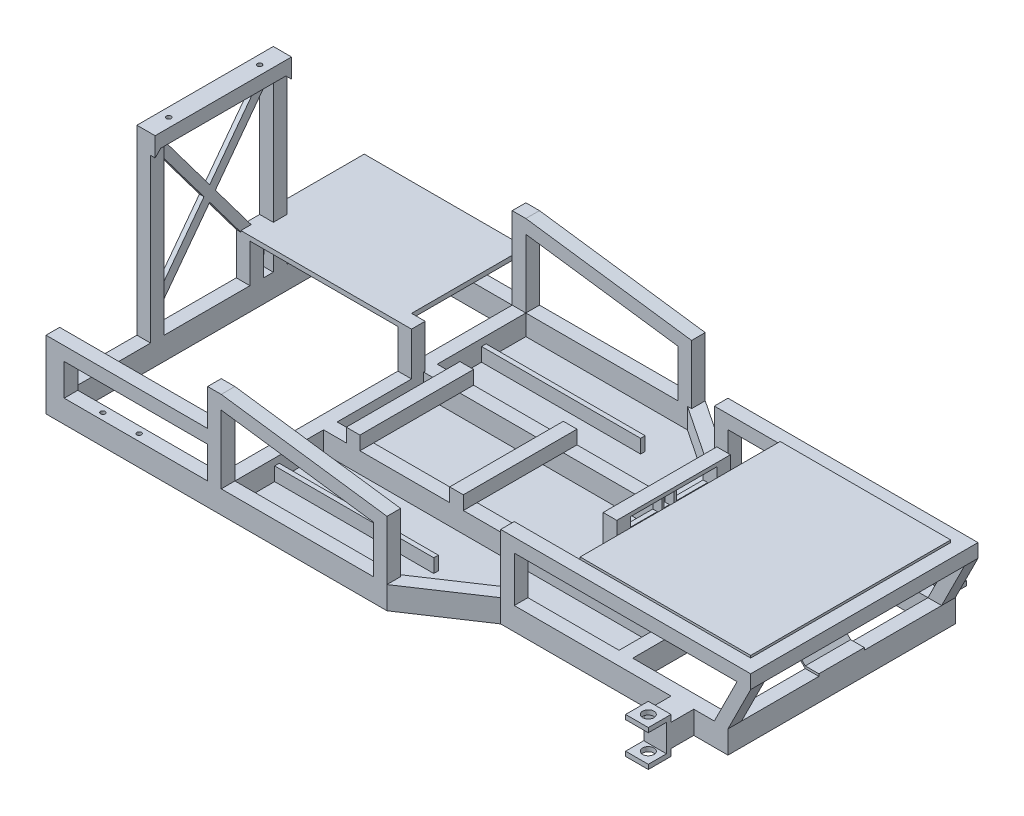
SolidWorks part; units mm, degrees
ref_plane "Front Plane" through (0, 0, 0) normal (0, 0, 1) x (1, 0, 0)
ref_plane "Top Plane" through (0, 0, 0) normal (0, 1, 0) x (1, 0, 0)
ref_plane "Right Plane" through (0, 0, 0) normal (1, 0, 0) x (0, 0, -1)
sketch "Sketch1" plane through (0, 0, 0) normal (0, 1, 0) x (1, 0, 0)
  line L1 (-65, 35) -> (10, 35)
  line L2 (-65, 35) -> (-65, -35)
  line L3 (-65, -35) -> (10, -35)
  line L4 (75, 25) -> (75, -25)
  line L6 (25, 25) -> (10, 35)
  line L9 (25, -25) -> (10, -35)
  line L10 (25, 25) -> (75, 25)
  line L11 (25, -25) -> (75, -25)
  line L12 (-62, 32) -> (-62, -32)
  line L13 (-62, -32) -> (-29.4542, -32)
  line L14 (24.0917, -22) -> (9.0917, -32)
  line L15 (24.0917, -22) -> (48.0458, -22)
  line L16 (72, 22) -> (72, -22)
  line L17 (24.0917, 22) -> (48.0458, 22)
  line L18 (24.0917, 22) -> (9.0917, 32)
  line L19 (-62, 32) -> (-29.4542, 32)
  line L20 (-26.4542, 32) -> (-26.4542, 12.5)
  line L21 (-29.4542, 32) -> (-29.4542, -32)
  line L22 (-26.4542, 32) -> (9.0917, 32)
  line L23 (-62, 32) -> (9.0917, 32) construction
  line L24 (-26.4542, -32) -> (9.0917, -32)
  line L25 (-62, -32) -> (9.0917, -32) construction
  line L27 (51.0458, 22) -> (51.0458, -22)
  line L28 (51.0458, 22) -> (72, 22)
  line L29 (24.0917, 22) -> (72, 22) construction
  line L30 (51.0458, -22) -> (72, -22)
  line L31 (24.0917, -22) -> (72, -22) construction
  line L32 (48.0458, 22) -> (48.0458, 12.5)
  line L33 (48.0458, 12.5) -> (-26.4542, 12.5)
  line L34 (-26.4542, -12.5) -> (-26.4542, -32)
  line L35 (-26.4542, 9.5) -> (48.0458, 9.5)
  line L36 (75, 0) -> (-65, 0) construction
  line L37 (48.0458, -12.5) -> (-26.4542, -12.5)
  line L38 (-26.4542, -9.5) -> (48.0458, -9.5)
  line L39 (48.0458, 9.5) -> (48.0458, -9.5)
  line L41 (48.0458, -12.5) -> (48.0458, -22)
  line L42 (-26.4542, 9.5) -> (-26.4542, -9.5)
  line L43 (-26.4542, 32) -> (-26.4542, -32) construction
  point P0 (0, 0)
  dimension "D1" = 70
  dimension "D2" = 75
  dimension "D3" = 75
  dimension "D4" = 50
  dimension "D6" = 3
  dimension "D7" = 15
  dimension "D5" = 3
extrude "Boss-Extrude1" add sketch "Sketch1" along normal mid plane 5
sketch "Sketch2" plane through (0, -2.5, 0) normal (0, -1, 0) x (1, 0, 0)
  line L0 (9.0917, 32) -> (24.0917, 22)
  line L1 (-26.4542, 32) -> (9.0917, 32)
  line L2 (-26.4542, 32) -> (-26.4542, -32)
  line L3 (-26.4542, -32) -> (9.0917, -32)
  line L5 (24.0917, 22) -> (48.0458, 22)
  line L6 (48.0458, 22) -> (48.0458, -22)
  line L7 (48.0458, -22) -> (24.0917, -22)
  line L8 (24.0917, -22) -> (9.0917, -32)
extrude "Boss-Extrude3" add sketch "Sketch2" against normal blind 0.5
sketch "Sketch3" plane through (0, 0, 25) normal (0, 0, 1) x (1, 0, 0)
  line L2 (25, -2.5) -> (75, -2.5) construction
  line L3 (62.4798, 2.5) -> (67.4798, 2.5)
  line L4 (62.4798, 2.5) -> (62.4798, -2.5)
  line L5 (62.4798, -2.5) -> (67.4798, -2.5)
  line L6 (67.4798, 2.5) -> (67.4798, -2.5)
  line L7 (62.4798, 2.5) -> (67.4798, -2.5) construction
  line L8 (62.4798, -2.5) -> (67.4798, 2.5) construction
  dimension "D1" = 5
  dimension "D2" = 5
extrude "Boss-Extrude4" add sketch "Sketch3" along normal blind 5
sketch "Sketch6" plane through (0, 0, 30) normal (0, 0, 1) x (1, 0, 0)
  line L0 (75, 2.5) -> (75, -2.5) construction
  line L1 (62.4798, 4) -> (67.4798, 4)
  line L2 (62.4798, 4) -> (62.4798, -4)
  line L3 (62.4798, -4) -> (67.4798, -4)
  line L4 (67.4798, 4) -> (67.4798, -4)
  point P0 (64.9798, 0)
  point P5 (64.9798, 4)
  point P9 (75, 0)
  dimension "D1" = 8
  dimension "D2" = 5
  dimension "D4" = 4
extrude "Boss-Extrude5" add sketch "Sketch6" along normal blind 1
sketch "Sketch7" plane through (0, 4, 0) normal (0, 1, 0) x (1, 0, 0)
  line L0 (62.4798, -30) -> (67.4798, -30)
  line L1 (67.4798, -30) -> (67.4798, -35)
  line L2 (67.4798, -35) -> (62.4798, -35)
  line L3 (62.4798, -35) -> (62.4798, -30)
extrude "Boss-Extrude7" add sketch "Sketch7" against normal blind 8
sketch "Sketch8" plane through (0, 0, 35) normal (0, 0, 1) x (1, 0, 0)
  line L9 (62.4798, -4) -> (62.4798, 4) construction
  line L10 (62.4798, 3) -> (67.4798, 3)
  line L11 (67.4798, -4) -> (67.4798, 4) construction
  line L12 (67.4798, 3) -> (67.4798, -3)
  line L13 (67.4798, -3) -> (62.4798, -3)
  line L14 (62.4798, -3) -> (62.4798, 3)
extrude "Cut-Extrude1" cut sketch "Sketch8" against normal blind 4
sketch "Sketch9" plane through (0, 4, 0) normal (0, 1, 0) x (1, 0, 0)
  circle A0 centre (64.9798, -32.5) radius 1.25
  dimension "D1" = 2.5
extrude "Cut-Extrude2" cut sketch "Sketch9" against normal through all
sketch "Sketch10" plane through (0, 0, -25) normal (0, 0, -1) x (-1, 0, 0)
  line L3 (-67.4798, 2.5) -> (-62.4798, 2.5)
  line L4 (-67.4798, 2.5) -> (-67.4798, -2.5)
  line L5 (-67.4798, -2.5) -> (-62.4798, -2.5)
  line L6 (-62.4798, 2.5) -> (-62.4798, -2.5)
  dimension "D1" = 5
  dimension "D2" = 5
extrude "Boss-Extrude10" add sketch "Sketch10" along normal blind 5
sketch "Sketch12" plane through (0, 0, -30) normal (0, 0, -1) x (-1, 0, 0)
  line L2 (-67.4798, 4) -> (-62.4798, 4)
  line L3 (-67.4798, 4) -> (-67.4798, -4)
  line L4 (-67.4798, -4) -> (-62.4798, -4)
  line L5 (-62.4798, 4) -> (-62.4798, -4)
extrude "Boss-Extrude11" add sketch "Sketch12" along normal blind 5
sketch "Sketch13" plane through (0, 0, -35) normal (0, 0, -1) x (-1, 0, 0)
  line L1 (-67.4798, 4) -> (-67.4798, -4) construction
  line L2 (-67.4798, 3) -> (-62.4798, 3)
  line L3 (-62.4798, -4) -> (-62.4798, 4) construction
  line L4 (-62.4798, 3) -> (-62.4798, -3)
  line L5 (-62.4798, -3) -> (-67.4798, -3)
  line L6 (-67.4798, -3) -> (-67.4798, 3)
extrude "Cut-Extrude3" cut sketch "Sketch13" against normal blind 4
sketch "Sketch14" plane through (0, 4, 0) normal (0, 1, 0) x (1, 0, 0)
  circle A0 centre (64.9798, 32.5) radius 1.25
extrude "Cut-Extrude4" cut sketch "Sketch14" against normal through all
sketch "Sketch16" plane through (-65, 0, 0) normal (-1, 0, 0) x (0, 0, 1)
  line L1 (35, 2.5) -> (35, 22.5)
  line L3 (-35, 22.5) -> (-35, 2.5)
  line L4 (-35, 22.5) -> (-15, 42.5)
  line L5 (-15, 42.5) -> (15, 42.5)
  line L6 (15, 42.5) -> (35, 22.5)
  line L7 (-32, 21.2574) -> (-13.7574, 39.5)
  line L8 (-13.7574, 39.5) -> (13.7574, 39.5)
  line L9 (13.7574, 39.5) -> (32, 21.2574)
  line L10 (32, 5.5) -> (32, 21.2574)
  line L12 (-32, 21.2574) -> (-32, 5.5)
  line L13 (-32, 5.5) -> (32, 5.5) construction
  line L14 (-32, 5.5) -> (-32, 2.5)
  line L15 (32, 5.5) -> (32, 2.5)
  line L16 (-32, 2.5) -> (-35, 2.5)
  line L17 (-35, 2.5) -> (35, 2.5) construction
  line L18 (35, 2.5) -> (32, 2.5)
  point P12 (0, 42.5)
  dimension "D1" = 3
extrude "Boss-Extrude12" add sketch "Sketch16" against normal blind 4
sketch "Sketch19" plane through (0, 2.5, 0) normal (0, 1, 0) x (1, 0, 0)
  line L0 (10, 35) -> (-61, 35) construction
  line L1 (-29.4542, 32) -> (-26.4542, 32)
  line L2 (-29.4542, 32) -> (-29.4542, 35)
  line L3 (-29.4542, 35) -> (-26.4542, 35)
  line L4 (-26.4542, 32) -> (-26.4542, 35)
  line L5 (-61, -35) -> (10, -35) construction
  line L6 (-29.4542, -32) -> (-26.4542, -32)
  line L7 (-29.4542, -32) -> (-29.4542, -35)
  line L8 (-29.4542, -35) -> (-26.4542, -35)
  line L9 (-26.4542, -32) -> (-26.4542, -35)
extrude "Boss-Extrude13" add sketch "Sketch19" along normal blind 18
sketch "Sketch21" plane through (0, 2.5, 0) normal (0, 1, 0) x (1, 0, 0)
  line L0 (24.0917, -22) -> (48.0458, -22) construction
  line L1 (25, -25) -> (28, -25)
  line L2 (25, -25) -> (25, -22)
  line L3 (25, -22) -> (28, -22)
  line L4 (28, -25) -> (28, -22)
  line L5 (24.0917, 22) -> (48.0458, 22) construction
  line L6 (25, 25) -> (28, 25)
  line L7 (25, 25) -> (25, 22)
  line L8 (25, 22) -> (28, 22)
  line L9 (28, 25) -> (28, 22)
extrude "Boss-Extrude14" add sketch "Sketch21" along normal blind 10
sketch "Sketch22" plane through (0, 12.5, 0) normal (0, 1, 0) x (1, 0, 0)
  line L1 (25, 25) -> (80, 25)
  line L2 (25, 25) -> (25, 22)
  line L3 (25, 22) -> (80, 22)
  line L4 (80, 25) -> (80, 22)
  line L5 (25, -25) -> (80, -25)
  line L6 (25, -25) -> (25, -22)
  line L7 (25, -22) -> (80, -22)
  line L8 (80, -25) -> (80, -22)
extrude "Boss-Extrude15" add sketch "Sketch22" along normal blind 3
sketch "Sketch23" plane through (0, 0, 25) normal (0, 0, 1) x (1, 0, 0)
  line L0 (80, 12.5) -> (75, 2.5)
  line L1 (75, 2.5) -> (72, 2.5)
  line L2 (67.4798, 2.5) -> (75, 2.5) construction
  line L3 (72, 2.5) -> (77, 12.5)
  line L4 (28, 12.5) -> (80, 12.5) construction
  line L5 (77, 12.5) -> (80, 12.5)
extrude "Boss-Extrude17" add sketch "Sketch23" against normal blind 3
sketch "Sketch24" plane through (0, 0, -25) normal (0, 0, -1) x (-1, 0, 0)
  line L0 (-75, 2.5) -> (-80, 12.5)
  line L1 (-80, 12.5) -> (-77, 12.5)
  line L2 (-80, 12.5) -> (-28, 12.5) construction
  line L3 (-77, 12.5) -> (-72, 2.5) construction
  line L4 (-77, 12.5) -> (-72, 2.5)
  line L5 (-72, 2.5) -> (-75, 2.5)
extrude "Boss-Extrude18" add sketch "Sketch24" against normal blind 3
sketch "Sketch25" plane through (80, 0, 0) normal (1, 0, 0) x (0, 0, -1)
  line L0 (-22, 15.5) -> (22, 15.5)
  line L1 (22, 15.5) -> (22, 12.5)
  line L2 (22, 12.5) -> (-22, 12.5)
  line L3 (-22, 12.5) -> (-22, 15.5)
extrude "Boss-Extrude19" add sketch "Sketch25" against normal blind 3
sketch "Sketch31" plane through (0, -2.5, 0) normal (0, -1, 0) x (1, 0, 0)
  circle A0 centre (-46, 33.5) radius 0.5
  circle A1 centre (-54, 33.5) radius 0.5
  circle A2 centre (-54, -33.5) radius 0.5
  circle A3 centre (-46, -33.5) radius 0.5
extrude "Cut-Extrude5" cut sketch "Sketch31" against normal up to next
sketch "Sketch35" plane through (0, 0, 35) normal (0, 0, 1) x (1, 0, 0)
  line L0 (10, 2.5) -> (10, 12.5)
  line L1 (10, 12.5) -> (10, 15.5)
  line L2 (10, 15.5) -> (-26.4542, 20.5)
  line L3 (-26.4542, 20.5) -> (-26.4542, 17.5)
  line L4 (-26.4542, 20.5) -> (-26.4542, 2.5) construction
  line L5 (-26.4542, 17.5) -> (7, 12.9115)
  line L6 (10, 2.5) -> (7, 2.5)
  line L7 (-26.4542, 2.5) -> (10, 2.5) construction
  line L8 (7, 2.5) -> (7, 12.9115)
extrude "Boss-Extrude24" add sketch "Sketch35" against normal blind 3 separate body
sketch "Sketch36" plane through (0, 0, -35) normal (0, 0, -1) x (-1, 0, 0)
  line L0 (-10, 2.5) -> (-10, 15.5)
  line L1 (-10, 15.5) -> (26.4542, 20.5)
  line L2 (26.4542, 20.5) -> (26.4542, 17.5)
  line L3 (26.4542, 20.5) -> (26.4542, 2.5) construction
  line L4 (26.4542, 17.5) -> (-7, 12.9115)
  line L5 (-7, 12.9115) -> (-7, 2.5)
  line L6 (-7, 2.5) -> (-10, 2.5)
extrude "Boss-Extrude25" add sketch "Sketch36" against normal blind 3
sketch "Sketch38" plane through (0, 42.5, 0) normal (0, 1, 0) x (1, 0, 0)
  circle A0 centre (-63, 10) radius 0.5
  circle A1 centre (-63, -10) radius 0.5
extrude "Cut-Extrude6" cut sketch "Sketch38" against normal up to next (3 mm away)
sketch "Sketch40" plane through (-29.4542, 0, 0) normal (-1, 0, 0) x (0, 0, 1)
  line L0 (-35, 12) -> (-35, 11)
  line L1 (-35, 20.5) -> (-35, 2.5) construction
  line L2 (-35, 11) -> (-6.8573, 11)
  line L4 (-6.8573, 12) -> (-35, 12)
  line L6 (-6.8573, 12) -> (-6.8573, 11)
  point P5 (-35, 11.5)
  dimension "D1" = 1
extrude "Boss-Extrude26" add sketch "Sketch40" along normal through all
sketch "Sketch43" plane through (-65, 0, 0) normal (-1, 0, 0) x (0, 0, 1)
  line L0 (-6.8573, 12) -> (-6.8573, 2.5)
  line L1 (-32, 2.5) -> (32, 2.5) construction
  line L2 (-6.8573, 2.5) -> (-9.8573, 2.5)
  line L3 (-9.8573, 2.5) -> (-9.8573, 12)
  line L5 (-6.8573, 12) -> (-9.8573, 12)
  line L6 (-6.8573, 12) -> (-32, 12) construction
extrude "Boss-Extrude31" add sketch "Sketch43" against normal blind 3
sketch "Sketch44" plane through (-29.4542, 0, 0) normal (1, 0, 0) x (0, 0, -1)
  line L0 (6.8573, 12) -> (6.8573, 2.5)
  line L1 (6.8573, 2.5) -> (9.8573, 2.5)
  line L2 (-22, 2.5) -> (22, 2.5) construction
  line L3 (9.8573, 11) -> (9.8573, 2.5) construction
  line L4 (9.8573, 2.5) -> (9.8573, 12)
  line L5 (6.8573, 12) -> (32, 12) construction
  line L6 (9.8573, 12) -> (6.8573, 12)
extrude "Boss-Extrude32" add sketch "Sketch44" along normal blind 3
sketch "Sketch46" plane through (0, -2, 0) normal (0, 1, 0) x (1, 0, 0)
  line L0 (-26.4542, 22.25) -> (8.5458, 22.25)
  line L1 (-26.4542, 32) -> (-26.4542, 12.5) construction
  line L2 (8.5458, 22.25) -> (8.5458, 23.25)
  line L3 (8.5458, 23.25) -> (-26.4542, 23.25)
  line L4 (-26.4542, 23.25) -> (-26.4542, 22.25)
  dimension "D1" = 1
extrude "Boss-Extrude33" add sketch "Sketch46" along normal blind 3
sketch "Sketch47" plane through (0, 2.5, 0) normal (0, 1, 0) x (1, 0, 0)
  line L0 (75, 0) -> (75, 5)
  line L1 (75, -22) -> (75, 22) construction
  line L2 (75, 5) -> (72, 5)
  line L3 (72, -22) -> (72, 22) construction
  line L4 (72, 5) -> (72, -5)
  line L5 (72, -5) -> (75, -5)
  line L6 (75, -5) -> (75, 0)
extrude "Boss-Extrude34" add sketch "Sketch47" along normal blind 0.5
sketch "Sketch48" plane through (0, 0, 5) normal (0, 0, 1) x (1, 0, 0)
  line L2 (69.8787, 4.6213) -> (72, 2.5)
  line L3 (72, 3) -> (72, 2.5) construction
  line L4 (72, 3) -> (69.8787, 5.1213)
  line L5 (69.8787, 4.6213) -> (69.8787, 5.1213)
  line L6 (72, 2.5) -> (72, 3)
  dimension "D1" = 45
  dimension "D2" = 3
  dimension "D3" = 3
extrude "Boss-Extrude35" add sketch "Sketch48" against normal blind 10
sketch "Sketch49" plane through (0, 2.5, 0) normal (0, 1, 0) x (1, 0, 0)
  line L0 (38.0458, -9.5) -> (35.0458, -9.5)
  line L1 (-26.4542, 12.5) -> (48.0458, 12.5) construction
  line L2 (38.0458, 12.5) -> (38.0458, 9.5)
  line L3 (48.0458, 9.5) -> (-26.4542, 9.5) construction
  line L4 (38.0458, 9.5) -> (35.0458, 9.5)
  line L5 (35.0458, 9.5) -> (35.0458, 12.5)
  line L6 (35.0458, 12.5) -> (38.0458, 12.5)
  line L7 (48.0458, -9.5) -> (-26.4542, -9.5) construction
  line L8 (35.0458, -9.5) -> (35.0458, -12.5)
  line L9 (48.0458, -12.5) -> (-26.4542, -12.5) construction
  line L10 (35.0458, -12.5) -> (38.0458, -12.5)
  line L11 (-26.4542, -12.5) -> (48.0458, -12.5) construction
  line L12 (38.0458, -12.5) -> (38.0458, -9.5)
extrude "Boss-Extrude36" add sketch "Sketch49" along normal blind 15
sketch "Sketch51" plane through (-65, 0, 0) normal (-1, 0, 0) x (0, 0, 1)
  line L0 (-15, 42.5) -> (-15, 2.5)
  line L1 (-32, 2.5) -> (-9.8573, 2.5) construction
  line L2 (-15, 2.5) -> (-12, 2.5)
  line L3 (-12, 2.5) -> (-12, 42.5)
  line L4 (15, 42.5) -> (-15, 42.5) construction
  line L5 (-12, 42.5) -> (-15, 42.5)
  line L6 (15, 42.5) -> (15, -2.5)
  line L7 (-35, -2.5) -> (35, -2.5) construction
  line L8 (15, -2.5) -> (12, -2.5)
  line L9 (12, -2.5) -> (12, 42.5)
  line L10 (12, 42.5) -> (15, 42.5)
extrude "Boss-Extrude37" add sketch "Sketch51" against normal blind 3
sketch "Sketch52" plane through (-65, 0, 0) normal (-1, 0, 0) x (0, 0, 1)
  line L0 (-32, 12) -> (-35, 12)
  line L1 (-35, 22.5) -> (-35, -2.5) construction
  line L2 (-35, 12) -> (-35, 22.5)
  line L3 (-35, 22.5) -> (-15, 42.5)
  line L4 (-15, 42.5) -> (-15, 12)
  line L5 (-15, 38.2574) -> (-15, 12) construction
  line L6 (-15, 12) -> (-32, 12) construction
  line L7 (-15, 12) -> (-32, 12)
  line L10 (22, 12.5) -> (-22, 12.5) construction
  line L11 (15, 2.5) -> (15, 38.2574) construction
  line L12 (15, 12.5) -> (35, 12.5)
  line L13 (35, 22.5) -> (35, -2.5) construction
  line L14 (35, 12.5) -> (35, 22.5)
  line L15 (35, 22.5) -> (15, 42.5)
  line L19 (15, 42.5) -> (15, 12.5)
extrude "Cut-Extrude8" cut sketch "Sketch52" against normal blind 4
sketch "Sketch53" plane through (0, 0, 35) normal (0, 0, 1) x (1, 0, 0)
  line L0 (-65, 12.5) -> (-26.4542, 12.5)
  line L1 (-26.4542, 20.5) -> (-26.4542, 2.5) construction
  line L2 (-26.4542, 12.5) -> (-26.4542, 9.5)
  line L3 (-26.4542, 9.5) -> (-65, 9.5)
  line L4 (-65, 12.5) -> (-65, -2.5) construction
  line L5 (-65, 9.5) -> (-65, 12.5)
extrude "Boss-Extrude38" add sketch "Sketch53" against normal blind 3
sketch "Sketch54" plane through (0, 17.5, 0) normal (0, 1, 0) x (1, 0, 0)
  line L0 (35.0458, 12.5) -> (35.0458, -12.5)
  line L1 (35.0458, -12.5) -> (38.0458, -12.5)
  line L2 (38.0458, -12.5) -> (38.0458, 12.5)
  line L3 (38.0458, 12.5) -> (35.0458, 12.5)
extrude "Boss-Extrude39" add sketch "Sketch54" against normal blind 0.8
sketch "Sketch55" plane through (35.0458, 0, 0) normal (-1, 0, 0) x (0, 0, 1)
  line L1 (9.5, 16.7) -> (9.5, 2.5) construction
  line L2 (9.5, 12.7) -> (-12.5, 12.7)
  line L3 (-12.5, 17.5) -> (-12.5, 2.5) construction
  line L4 (-12.5, 12.7) -> (-12.5, 10.7)
  line L5 (-12.5, 10.7) -> (9.5, 10.7)
  line L6 (9.5, 10.7) -> (9.5, 12.7)
extrude "Boss-Extrude40" add sketch "Sketch55" against normal blind 1
sketch "Sketch56" plane through (35.0458, 0, 0) normal (-1, 0, 0) x (0, 0, 1)
  line L0 (2.1318, 17.5) -> (2.1318, 12.7)
  line L1 (-12.5, 17.5) -> (12.5, 17.5) construction
  line L2 (9.5, 12.7) -> (-9.5, 12.7) construction
  line L3 (2.1318, 12.7) -> (2.6318, 12.7)
  line L4 (2.6318, 12.7) -> (2.6318, 17.5)
  line L5 (2.6318, 17.5) -> (2.1318, 17.5)
  line L6 (-0.1503, 17.5) -> (-0.1503, 12.7)
  line L7 (-0.1503, 12.7) -> (-0.6503, 12.7)
  line L8 (-0.6503, 12.7) -> (-0.6503, 17.5)
  line L9 (-0.6503, 17.5) -> (-0.1503, 17.5)
extrude "Boss-Extrude41" add sketch "Sketch56" against normal blind 1
sketch "Sketch57" plane through (35.0458, 0, 0) normal (-1, 0, 0) x (0, 0, 1)
  line L0 (-9.5, 16.7) -> (9.5, 16.7)
  line L1 (9.5, 16.7) -> (9.5, 12.7)
  line L2 (9.5, 12.7) -> (-9.5, 12.7)
  line L3 (-9.5, 16.7) -> (-9.5, 12.7) construction
  line L4 (-0.6503, 12.7) -> (-9.5, 12.7) construction
  line L5 (-9.5, 12.7) -> (-9.5, 16.7)
extrude "Cut-Extrude9" cut sketch "Sketch57" against normal mid plane 10
sketch "Sketch58" plane through (35.0458, 0, 0) normal (-1, 0, 0) x (0, 0, 1)
  line L0 (1.0748, 17.5) -> (1.0748, 12.7)
  line L1 (-12.5, 17.5) -> (12.5, 17.5) construction
  line L2 (9.5, 12.7) -> (-9.5, 12.7) construction
  line L3 (1.0748, 12.7) -> (1.5748, 12.7)
  line L4 (1.5748, 12.7) -> (1.5748, 17.5)
  line L5 (1.5748, 17.5) -> (1.0748, 17.5)
  line L10 (-1.0873, 12.7) -> (-1.0873, 17.5)
  line L11 (-1.0873, 17.5) -> (-1.5873, 17.5)
  line L12 (-1.5873, 17.5) -> (-1.5873, 12.7)
  line L13 (-1.5873, 12.7) -> (-1.0873, 12.7)
extrude "Boss-Extrude42" add sketch "Sketch58" against normal blind 2
sketch "Sketch59" plane through (0, 2.5, 0) normal (0, 1, 0) x (1, 0, 0)
  line L1 (48.0458, 12.5) -> (-26.4542, 12.5) construction
  line L2 (-21.4542, 12.5) -> (-21.4542, -12.5)
  line L3 (35.0458, -12.5) -> (-26.4542, -12.5) construction
  line L4 (-21.4542, -12.5) -> (-18.4542, -12.5)
  line L5 (-18.4542, -12.5) -> (-18.4542, 12.5)
  line L6 (-18.4542, 12.5) -> (-21.4542, 12.5)
  line L8 (-26.4542, -12.5) -> (48.0458, -12.5) construction
  line L9 (1.2958, -12.5) -> (1.2958, 12.5)
  line L10 (1.2958, 12.5) -> (4.2958, 12.5)
  line L11 (-26.4542, 12.5) -> (35.0458, 12.5) construction
  line L12 (4.2958, 12.5) -> (4.2958, -12.5)
  line L13 (4.2958, -12.5) -> (1.2958, -12.5)
extrude "Boss-Extrude43" add sketch "Sketch59" along normal blind 3
sketch "Sketch60" plane through (0, -2, 0) normal (0, 1, 0) x (1, 0, 0)
  line L1 (-26.4542, -12.5) -> (-26.4542, -32) construction
  line L2 (-26.4542, -23.25) -> (8.5458, -23.25)
  line L3 (8.5458, -23.25) -> (8.5458, -22.25)
  line L4 (8.5458, -22.25) -> (-26.4542, -22.25)
  line L5 (-26.4542, -32) -> (-26.4542, -12.5) construction
  line L6 (-26.4542, -22.25) -> (-26.4542, -23.25)
extrude "Boss-Extrude44" add sketch "Sketch60" along normal blind 3
sketch "Sketch61" plane through (-65, 0, 0) normal (-1, 0, 0) x (0, 0, 1)
  line L0 (-1.25, 22.5) -> (-15, 4.1667)
  line L1 (0, 20.8333) -> (-13.4, 2.9667)
  line L2 (13.75, 42.5) -> (0, 24.1667)
  line L3 (-15, 40.8333) -> (-1.25, 22.5)
  line L4 (-13.4, 42.0333) -> (0, 24.1667)
  line L5 (15.35, 41.3) -> (1.25, 22.5)
  line L6 (-15, 4.1667) -> (-13.4, 2.9667)
  line L7 (-15, 11) -> (-15, 2.5) construction
  line L8 (13.75, 42.5) -> (15.35, 41.3)
  line L9 (15, 42.5) -> (-15, 42.5) construction
  line L10 (-15, 40.8333) -> (-13.4, 42.0333)
  line L11 (-15, 42.5) -> (-15, 12) construction
  line L12 (15, 4.1667) -> (13.4, 2.9667)
  line L13 (15, 2.5) -> (15, 42.5) construction
  line L14 (1.25, 22.5) -> (15, 4.1667)
  line L15 (0, 20.8333) -> (13.4, 2.9667)
extrude "Boss-Extrude45" add sketch "Sketch61" against normal blind 1
sketch "Sketch62" plane through (-65, 0, 0) normal (-1, 0, 0) x (0, 0, 1)
  line L0 (15, 41.5625) -> (15, 40.8333)
  line L1 (15, 40.8333) -> (15.35, 41.3)
  line L2 (15.35, 41.3) -> (15, 41.5625)
extrude "Cut-Extrude10" cut sketch "Sketch62" against normal blind 1
sketch "Sketch64" plane through (0, 15.5, 0) normal (0, 1, 0) x (1, 0, 0)
  line L1 (77, 22) -> (77, -22)
  line L4 (39.4895, 22) -> (39.4895, -22)
  line L5 (39.4895, 22) -> (77, 22)
  line L6 (39.4895, -22) -> (77, -22)
extrude "Boss-Extrude49" add sketch "Sketch64" along normal blind 0.5 separate body
